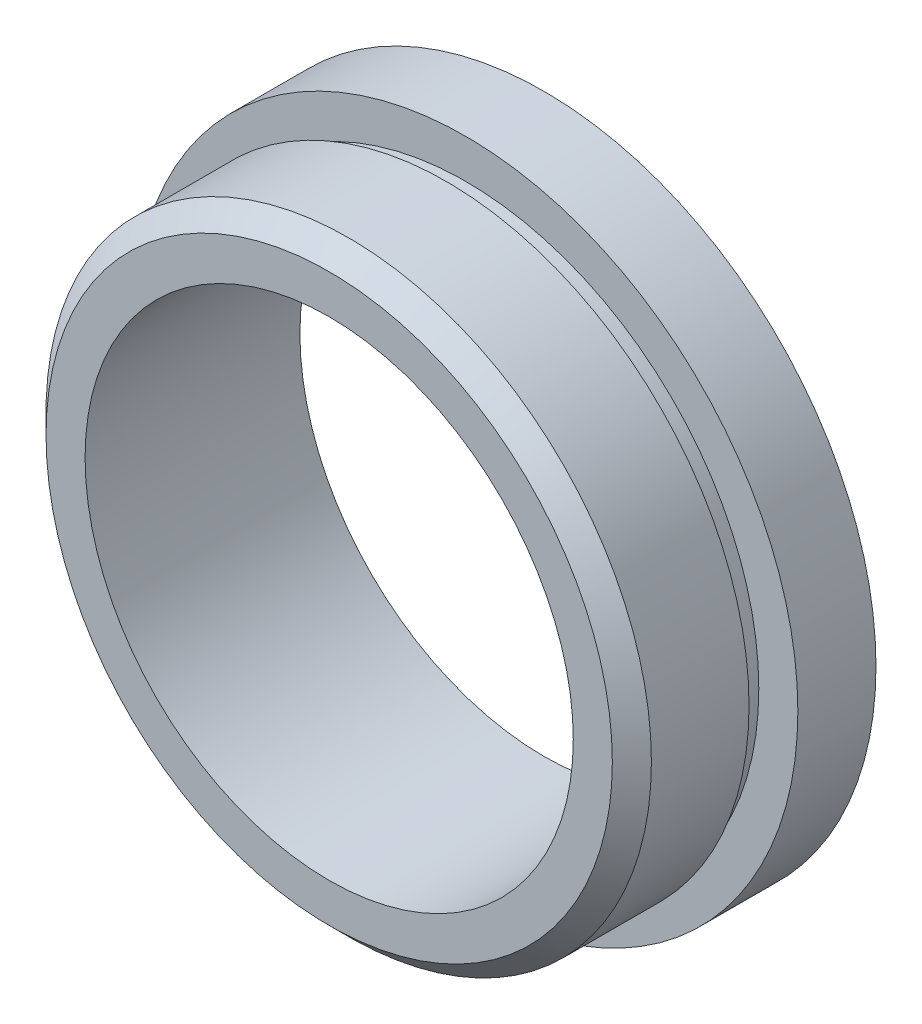
SolidWorks part; units mm, degrees
material "Zinc AC41A Alloy, As Cast"
ref_plane "Plan de face" through (0, 0, 0) normal (0, 0, 1) x (1, 0, 0)
ref_plane "Plan de dessus" through (0, 0, 0) normal (0, 1, 0) x (1, 0, 0)
ref_plane "Plan de droite" through (0, 0, 0) normal (1, 0, 0) x (0, 0, -1)
sketch "Sketch1" plane through (0, 0, 0) normal (0, 0, 1) x (1, 0, 0)
  circle A0 centre (0, 0) radius 12.5
  circle A1 centre (0, 0) radius 17
  dimension "D1" = 25
  dimension "D2" = 34
extrude "Boss-Extrude1" add sketch "Sketch1" along normal blind 4
sketch "Sketch2" plane through (0, 0, 4) normal (0, 0, 1) x (1, 0, 0)
  circle A0 centre (0, 0) radius 15
  circle A1 centre (0, 0) radius 12.5
  dimension "D1" = 30
  dimension "D2" = 25
extrude "Boss-Extrude2" add sketch "Sketch2" along normal blind 1
sketch "Sketch3" plane through (0, 0, 5) normal (0, 0, 1) x (1, 0, 0)
  circle A0 centre (0, 0) radius 15.5
  circle A1 centre (0, 0) radius 12.5
  dimension "D1" = 31
  dimension "D2" = 25
extrude "Boss-Extrude3" add sketch "Sketch3" along normal blind 6
cosmetic thread "Cosmetic Thread1" parameters "D2"=30
chamfer "Chamfer1" distance 1 angle 45 1 edges at (15.5, 0, 11)
sketch "Sketch6" plane through (0, 0, 0) normal (1, 0, 0) x (0, 0, -1)
  line L0 (0, 17) -> (0, 14.5) construction
  line L1 (0, -17) -> (0, 17) construction
  line L3 (0, 14.5) -> (0, 15.6)
  line L4 (0, 15.6) -> (-1.5609, 14.6719)
  line L9 (-1.6587, 14.5) -> (0, 14.5)
  arc A0 (-1.6587, 14.5) -> (-1.5609, 14.6719) centre (-1.4587, 14.5) cw
  dimension "D6" = 0.9281
  dimension "D1" = 2.5
  dimension "D2" = 1.5609
  dimension "D3" = 1.6587
  dimension "D4" = 1.1
revolve "Cut-Revolve4" cut sketch "Sketch6" angle 360 about L9
